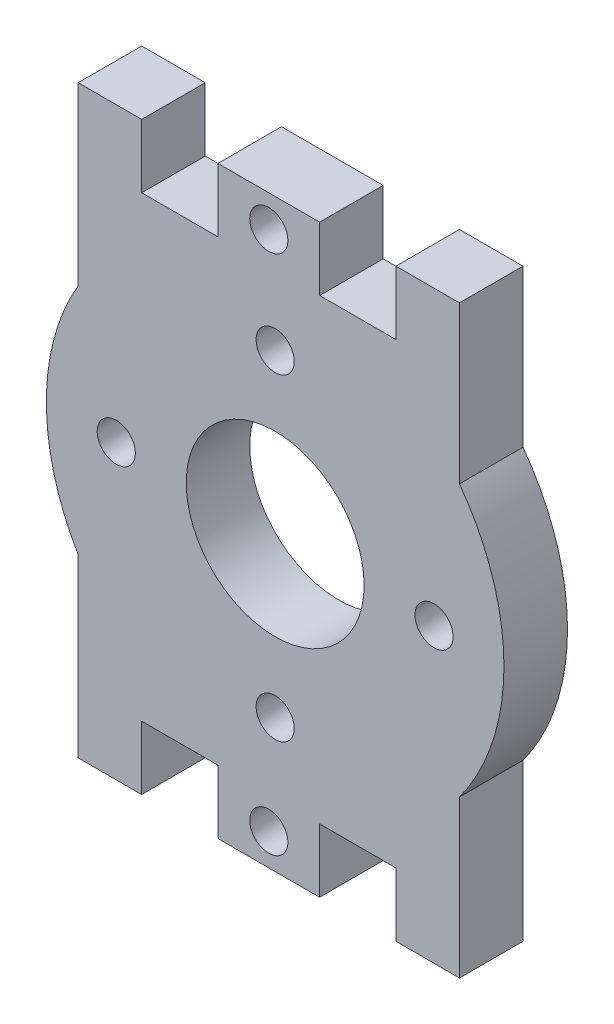
SolidWorks part; units mm, degrees
ref_plane "Front Plane" through (0, 0, 0) normal (0, 0, 1) x (1, 0, 0)
ref_plane "Top Plane" through (0, 0, 0) normal (0, 1, 0) x (1, 0, 0)
ref_plane "Right Plane" through (0, 0, 0) normal (1, 0, 0) x (0, 0, -1)
sketch "Sketch1" plane through (0, 0, 0) normal (0, 0, 1) x (1, 0, 0)
  line L0 (0, 0) -> (0, -25) construction
  line L1 (18, -984.2987) -> (18, 49015.7013) construction
  line L2 (12, 23) -> (9.5, 23)
  line L3 (12, 23) -> (12, 13.4164)
  line L4 (12, -23) -> (9.5, -23)
  line L5 (-12, 23) -> (-12, 13.4164)
  line L7 (12, -23) -> (-12, 23) construction
  line L8 (-12, -13.4164) -> (-12, -23)
  line L9 (12, -13.4164) -> (12, -23)
  line L10 (3.5, -20.5) -> (-4.5, -20.5) construction
  line L11 (-10.5, -23) -> (-12, -23)
  line L12 (9.5, -23) -> (9.5, -18)
  line L13 (9.5, -18) -> (3.5, -18)
  line L14 (3.5, -23) -> (3.5, -18)
  line L15 (-1000, 0) -> (49000, 0) construction
  line L16 (-4.5, -23) -> (-4.5, -18)
  line L17 (-4.5, -18) -> (-10.5, -18)
  line L18 (-10.5, -23) -> (-10.5, -18)
  line L19 (3.5, -23) -> (-4.5, -23)
  line L20 (9.5, 23) -> (9.5, 18)
  line L21 (9.5, 18) -> (3.5, 18)
  line L22 (3.5, 23) -> (3.5, 18)
  line L23 (-10.5, 23) -> (-10.5, 18)
  line L24 (-4.5, 18) -> (-10.5, 18)
  line L25 (-4.5, 23) -> (-4.5, 18)
  line L26 (3.5, 23) -> (-4.5, 23)
  line L27 (-10.5, 23) -> (-12, 23)
  line L28 (12, -23) -> (12, -18) construction
  circle A0 centre (0, 0) radius 7
  arc A1 (-12, 13.4164) -> (-12, -13.4164) centre (0, 0) ccw
  circle A2 centre (0, -12.5) radius 1.5
  circle A3 centre (-12.5, 0) radius 1.5
  circle A4 centre (0, 12.5) radius 1.5
  circle A5 centre (12.5, 0) radius 1.5
  circle A6 centre (0, 0) radius 18 construction
  circle A7 centre (-0.5, -20.5) radius 1.5
  arc A8 (12, -13.4164) -> (12, 13.4164) centre (0, 0) ccw
  circle A9 centre (-0.5, 20.5) radius 1.5
  point P3 (-2.5, -12.5)
  dimension "D3" = 14
  dimension "D7" = 36
  dimension "D2" = 36
  dimension "D8" = 3
  dimension "D5" = 12.5
  dimension "D6" = 4
extrude "Boss-Extrude1" add sketch "Sketch1" along normal blind 5
sketch "Sketch3" plane through (0, 0, 0) normal (0, 0, -1) x (-1, 0, 0)
  line L0 (-9.5, 23) -> (-9.5, 18) construction
  line L1 (-12, 23) -> (-14.5, 23)
  line L2 (-12, 23) -> (-12, 10.6654)
  line L3 (-12, 10.6654) -> (-14.5, 10.6654)
  line L4 (-14.5, 23) -> (-14.5, 10.6654)
  line L6 (10.5, 23) -> (15.5, 23)
  line L7 (10.5, 23) -> (10.5, 9.1515)
  line L8 (10.5, 9.1515) -> (15.5, 9.1515)
  line L9 (15.5, 23) -> (15.5, 9.1515)
  arc A0 (-12, 13.4164) -> (-12, -13.4164) centre (0, 0) ccw construction
  arc A1 (12, -13.4164) -> (12, 13.4164) centre (0, 0) ccw construction
  dimension "D1" = 5
  dimension "D2" = 5
extrude "Boss-Extrude2" add sketch "Sketch3" against normal blind 5
mirror "Mirror1" about plane through (0, 0, 0) normal (0, 1, 0) of "Boss-Extrude2"
